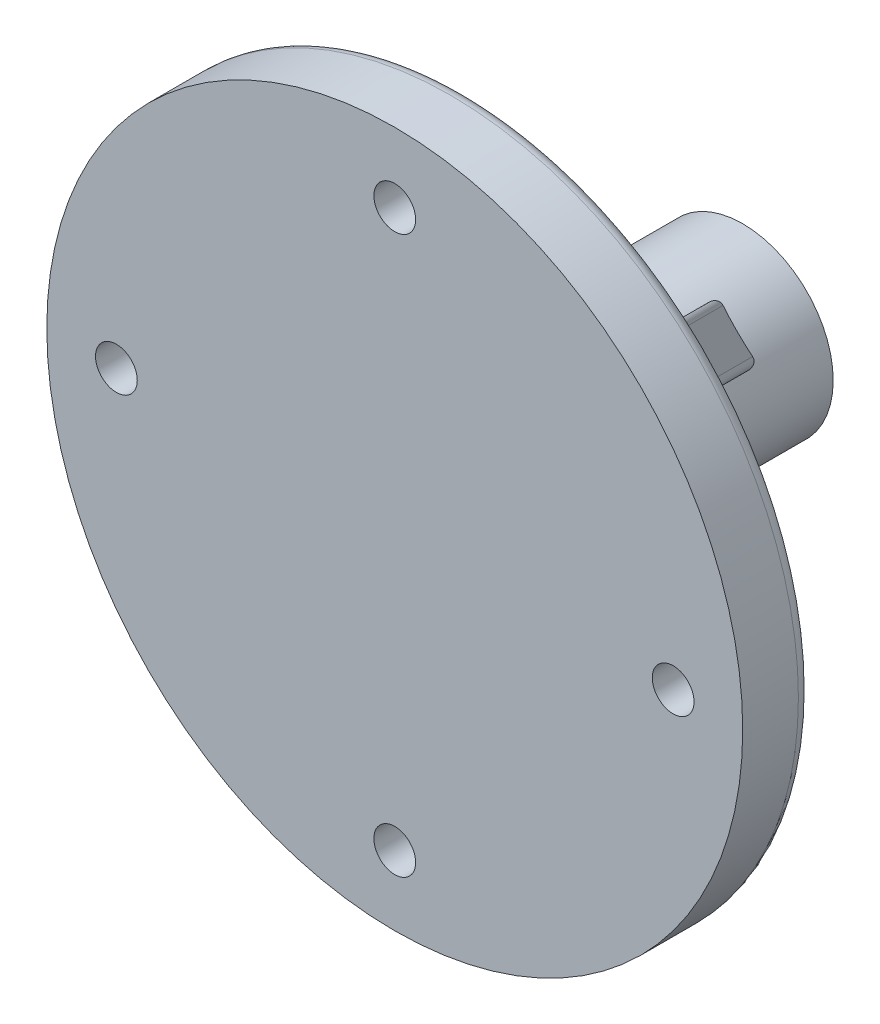
SolidWorks part; units mm, degrees
ref_plane "Спереди" through (0, 0, 0) normal (0, 0, 1) x (1, 0, 0)
ref_plane "Сверху" through (0, 0, 0) normal (0, 1, 0) x (1, 0, 0)
ref_plane "Справа" through (0, 0, 0) normal (1, 0, 0) x (0, 0, -1)
other "Configuration Table"
sketch "Sketch1" plane through (0, 0, 0) normal (0, 0, 1) x (1, 0, 0)
  circle A0 centre (0, 0) radius 6.5
  dimension "D1" = 13
extrude "Boss-Extrude1" add sketch "Sketch1" along normal blind 20 contours A0
sketch "Sketch4" plane through (0, 0, 0) normal (0, 0, -1) x (-1, 0, 0)
  circle A0 centre (0, 0) radius 2.5
  dimension "D1" = 5
extrude "Cut-Extrude1" cut sketch "Sketch4" against normal blind 15.5
fillet "Fillet1" radius 1 1 edges at (-2.5, 0, 15.5)
sketch "Sketch5" plane through (0, 0, 20) normal (0, 0, 1) x (1, 0, 0)
  circle A0 centre (0, 0) radius 25
  dimension "D1" = 50
extrude "Boss-Extrude2" add sketch "Sketch5" along normal blind 5
sketch "Sketch6" plane through (0, 0, 20) normal (0, 0, -1) x (-1, 0, 0)
  line L0 (-25, 0) -> (25, 0) construction
  line L1 (0, 25) -> (0, -25) construction
  line L2 (-17.6777, -17.6777) -> (17.6777, 17.6777) construction
  line L3 (17.6777, -17.6777) -> (-17.6777, 17.6777) construction
  circle A0 centre (0, 0) radius 25 construction
  circle A1 centre (0, 20) radius 1.5
  circle A2 centre (0, -20) radius 1.5
  circle A3 centre (-20, 0) radius 1.5
  circle A4 centre (20, 0) radius 1.5
  dimension "D3" = 3
  dimension "D1" = 45
  dimension "D2" = 45
  dimension "D4" = 40
  dimension "D5" = 40
extrude "Cut-Extrude2" cut sketch "Sketch6" against normal up to next
fillet "Fillet2" radius 5 1 edges at (6.5, 0, 20)
ref_plane "Plane1" through (0, 0, 0) normal (-0.7071, 0.7071, 0) x (0.7071, 0.7071, 0)
sketch "Sketch12" plane through (0, 0, 0) normal (-0.7071, 0.7071, 0) x (0.7071, 0.7071, 0)
  line L0 (6.5, -5) -> (21.5, -20)
  line L1 (6.5, -15) -> (6.5, 0) construction
  line L2 (25, -20) -> (-25, -20) construction
  dimension "D1" = 15
  dimension "D2" = 15
rib "Rib10" sketch "Sketch12" sketch "Sketch12" thickness 4 extrusion direction parallel to sketch draft on no parameters "D1"=4
pattern_circular "CirPattern1" count 4 over 360 about axis through (0, 0, 20) along (0, 0, 1) of "Rib10"
fillet "Fillet3" radius 1 1 edges at (25, 0, 20)
fillet "Fillet4" radius 0.5 8 edges at (8.3738, -11.2022, 12.3423) (11.2022, -8.3738, 12.3423) (-8.3738, -11.2022, 12.3423) (-11.2022, -8.3738, 12.3423) (11.2022, 8.3738, 12.3423) (8.3738, 11.2022, 12.3423) (-11.2022, 8.3738, 12.3423) (-8.3738, 11.2022, 12.3423)
sketch "Sketch13" plane through (0, 0, 20) normal (0, 0, -1) x (-1, 0, 0)
  circle A0 centre (-20, 0) radius 3
  circle A1 centre (0, 20) radius 3
  circle A2 centre (20, 0) radius 3
  circle A3 centre (0, -20) radius 3
  dimension "D1" = 6
extrude "Cut-Extrude3" cut sketch "Sketch13" against normal blind 1
